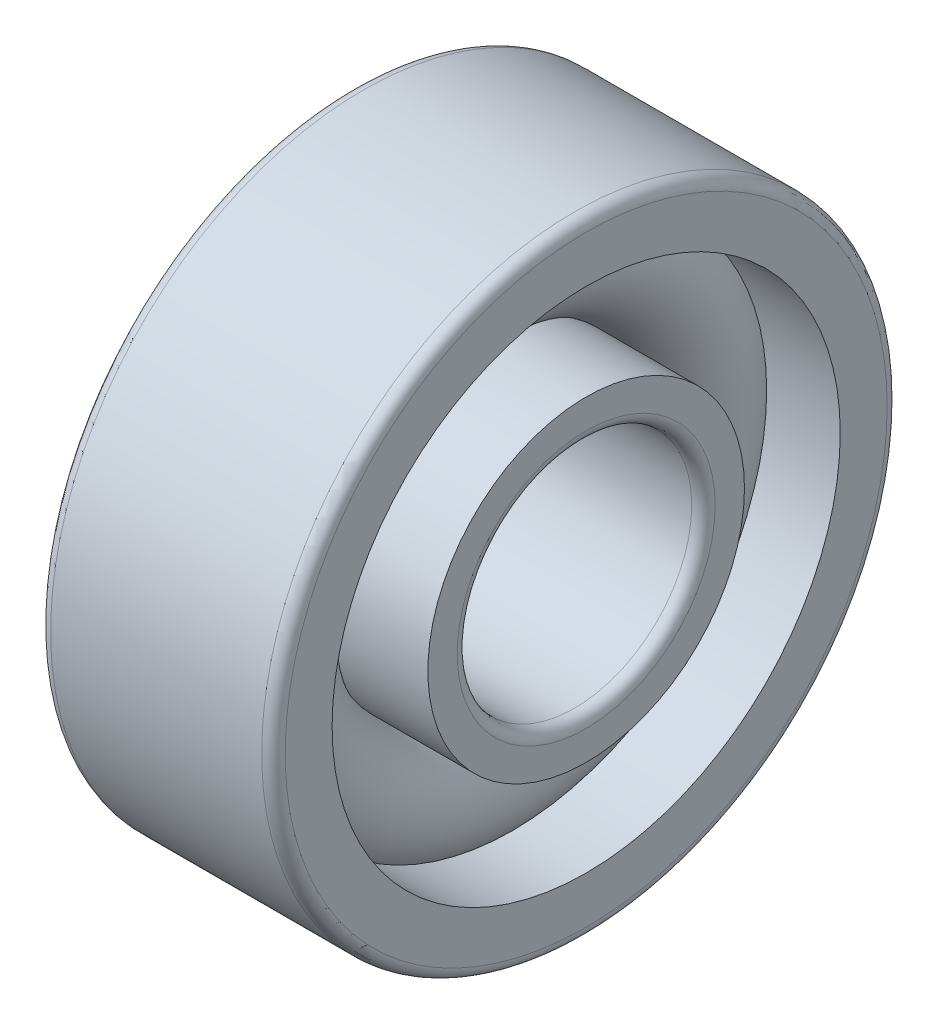
SolidWorks part; units mm, degrees
ref_plane "Plane1" through (0, 0, 0) normal (0, 0, 1) x (1, 0, 0)
ref_plane "Plane2" through (0, 0, 0) normal (0, 1, 0) x (1, 0, 0)
ref_plane "Plane3" through (0, 0, 0) normal (1, 0, 0) x (0, 0, -1)
sketch "Clipboard" plane through (0, 0, 0) normal (0, 0, 1) x (1, 0, 0)
  line L0 (-10, 0) -> (10, 0) construction
  line L1 (0, 0) -> (22.3471, -0.7804)
  line L2 (0, 0) -> (2.7483, 0.096)
  line L3 (0, 0) -> (22.3471, -0.7804)
  line L4 (0, 0) -> (-22.3573, -0.3902)
sketch "CagSpiSke" plane through (0, 0, 0) normal (0, 0, 1) x (1, 0, 0)
  line L0 (0.1875, 2.625) -> (0.1875, 2.875)
  line L1 (0.1875, 2.875) -> (-0.1875, 2.875)
  line L2 (-0.1875, 2.875) -> (-0.1875, 2.625)
  line L3 (-0.1875, 2.625) -> (0.1875, 2.625)
  line L4 (-20.6375, 0) -> (20.6375, 0) construction
  line L5 (0, 0) -> (0, 23.7692) construction
revolve "CageSpine" add sketch "CagSpiSke" angle 0.001 about L4
ref_axis "Axis1" through (-50, 0, 0) along (1, 0, 0)
sketch "CagBalSke" plane through (0, 0, 0) normal (0, 0, 1) x (1, 0, 0)
  line L0 (-0.825, 2.75) -> (0.825, 2.75)
  line L1 (-1.905, 2.75) -> (1.905, 2.75) construction
  line L2 (-10, 0) -> (10, 0) construction
  line L3 (0, 0) -> (0, 24) construction
  arc A0 (0.825, 2.75) -> (-0.825, 2.75) centre (0, 2.75) cw
revolve "CageBall" [suppressed] add sketch "CagBalSke" angle 360 about L1 reverse direction yes
pattern_circular "CageBalls" [suppressed] count 2 every 180 about axis through (-50, 0, 0) along (1, 0, 0)
sketch "CagTrmODSke" plane through (0, 0, 0) normal (0, 0, 1) x (1, 0, 0)
  line L0 (0.826, 2.875) -> (0.826, 3.576)
  line L1 (0.826, 3.576) -> (-0.826, 3.576)
  line L2 (-0.826, 3.576) -> (-0.826, 2.875)
  line L3 (-0.826, 2.875) -> (0.826, 2.875)
  line L4 (-20.6375, 0) -> (20.6375, 0) construction
  line L5 (0, 0) -> (0, 25) construction
revolve "CageTrimOD" [suppressed] cut sketch "CagTrmODSke" angle 360 about L4 reverse direction yes
sketch "CagTrmIDSke" plane through (0, 0, 0) normal (0, 0, 1) x (1, 0, 0)
  line L0 (0.826, 1.926) -> (0.826, 2.625)
  line L1 (0.826, 2.625) -> (-0.826, 2.625)
  line L2 (-0.826, 2.625) -> (-0.826, 1.926)
  line L3 (-0.826, 1.926) -> (0.826, 1.926)
  line L4 (-20.6375, 0) -> (20.6375, 0) construction
  line L5 (0, 0) -> (0, 25) construction
revolve "CageTrimID" [suppressed] cut sketch "CagTrmIDSke" angle 360 about L4 reverse direction yes
sketch "BalSimSke" plane through (0, 0, 0) normal (0, 0, 1) x (1, 0, 0)
  line L0 (-10, 0) -> (10, 0) construction
  line L1 (-10, 2.75) -> (10, 2.75) construction
  line L2 (0, 0) -> (0, 23) construction
  circle A0 centre (0, 2.75) radius 0.75
revolve "BallsSimplified" add sketch "BalSimSke" angle 360 about L0
sketch "BalDetSke" plane through (0, 0, 0) normal (0, 0, 1) x (1, 0, 0)
  line L0 (-0.75, 2.75) -> (0.75, 2.75)
  line L1 (-1.905, 2.75) -> (1.905, 2.75) construction
  line L2 (0, 0) -> (0, 25) construction
  arc A0 (0.75, 2.75) -> (-0.75, 2.75) centre (0, 2.75) cw
revolve "BallDetailed" [suppressed] add sketch "BalDetSke" angle 360 about L1 reverse direction yes
sketch "InnRacSke" plane through (0, 0, 0) normal (0, 0, 1) x (1, 0, 0)
  line L0 (-0.525, 2.25) -> (-1.5, 2.25)
  line L1 (-1.5, 2.25) -> (-1.5, 1.65)
  line L2 (-1.35, 1.5) -> (1.35, 1.5)
  line L3 (1.5, 1.65) -> (1.5, 2.025)
  line L4 (0, 2.025) -> (1.5, 2.025)
  line L5 (-20.6375, 0) -> (20.6375, 0) construction
  line L6 (0, 0) -> (0, 30) construction
  arc A0 (-1.5, 1.65) -> (-1.35, 1.5) centre (-1.35, 1.65) ccw
  arc A1 (1.35, 1.5) -> (1.5, 1.65) centre (1.35, 1.65) ccw
  arc A2 (0, 2.025) -> (-0.525, 2.25) centre (0, 2.75) cw
  dimension "Fillet_radius" = 0.15
revolve "InnerRace" add sketch "InnRacSke" angle 360 about L5 reverse direction yes
sketch "OutRacSke" plane through (0, 0, 0) normal (0, 0, 1) x (1, 0, 0)
  line L0 (0, 3.475) -> (-1.5, 3.475)
  line L1 (-1.5, 3.475) -> (-1.5, 3.85)
  line L2 (-1.35, 4) -> (1.35, 4)
  line L3 (1.5, 3.85) -> (1.5, 3.25)
  line L4 (1.5, 3.25) -> (0.525, 3.25)
  line L5 (-20.6375, 0) -> (20.6375, 0) construction
  line L6 (0, 0) -> (0, 30) construction
  arc A0 (-1.5, 3.85) -> (-1.35, 4) centre (-1.35, 3.85) cw
  arc A1 (1.35, 4) -> (1.5, 3.85) centre (1.35, 3.85) cw
  arc A2 (0.525, 3.25) -> (0, 3.475) centre (0, 2.75) ccw
  dimension "Fillet_radius" = 0.15
revolve "OuterRace" add sketch "OutRacSke" angle 360 about L5 reverse direction yes
pattern_circular "BallsDetailed" [suppressed] count 2 every 180 about axis through (-50, 0, 0) along (1, 0, 0)
equation "\"BallCLRad@Clipboard\" = ( \"OD@OutRacSke\" + \"ID@InnRacSke\" ) / 4"
equation "\"BallCLRad@BalSimSke\" = \"BallCLRad@Clipboard\""
equation "\"BallCLRad@BalDetSke\" = \"BallCLRad@Clipboard\""
equation "\"BallCLRad@InnRacSke\" = \"BallCLRad@Clipboard\""
equation "\"BallCLRad@OutRacSke\" = \"BallCLRad@Clipboard\""
equation "\"Ball_diameter@InnRacSke\" = \"Ball_diameter@BalDetSke\" - 0.05"
equation "\"Ball_diameter@OutRacSke\" = \"Ball_diameter@BalDetSke\" - 0.05"
equation "\"Ball_diameter@BalSimSke\" = \"Ball_diameter@BalDetSke\""
equation "\"Width@OutRacSke\" = \"Width@InnRacSke\""
equation "\"Fillet_radius@OutRacSke\" = \"Fillet_radius@InnRacSke\""
equation "\"Max_count@Clipboard\" = int( 3.14159265 / atn(( \"Ball_diameter@BalDetSke\" / 2) / sqr( \"BallCLRad@Clipboard\"  *  \"BallCLRad@Clipboard\" - ( \"Ball_diameter@BalDetSke\" / 2) *  ( \"Ball_diameter@BalDetSke\" / 2))))"
equation "\"Max_count@Clipboard\" = ((sgn( \"Max_count@Clipboard\" - \"Count@Clipboard\" )-1)*( \"Max_count@Clipboard\" - \"Count@Clipboard\" ))/-2+ \"Count@Clipboard\""
equation "\"Count@BallsDetailed\" = int( \"Show_count@Clipboard\" ) "
equation "\"Count@BallsDetailed\" = ((sgn( \"Count@BallsDetailed\" - \"Max_count@Clipboard\" )-1)*( \"Count@BallsDetailed\" - \"Max_count@Clipboard\" ))/-2+ \"Max_count@Clipboard\""
equation "\"Count@BallsDetailed\" = ((sgn( \"Count@BallsDetailed\" - \"Min_count@Clipboard\" )+1)*( \"Count@BallsDetailed\" - \"Min_count@Clipboard\"))/2 +\"Min_count@Clipboard\""
equation "\"Angle@BallsDetailed\" = 360.0 / \"Max_count@Clipboard\""
equation "\"BallCLRad@CagBalSke\" = \"BallCLRad@Clipboard\""
equation "\"Count@CageBalls\" = \"Count@BallsDetailed\""
equation "\"Angle@CageBalls\" = \"Angle@BallsDetailed\""
equation "\"Angle@CageSpine\" =  \"Angle@CageBalls\" * ( \"Count@CageBalls\" -1 + int( \"Count@CageBalls\" / \"Max_count@Clipboard\" ) )  + 0.001 -  int( \"Count@CageBalls\" / \"Max_count@Clipboard\" ) * 0.001"
equation "\"Angle@CageSpine\" =  \"Angle@CageSpine\" * int( \"Min_count@Clipboard\" / 2) + int(1 / \"Min_count@Clipboard\")  * 0.001"
equation "\"CageWallOD@CagBalSke\" =  \"Ball_diameter@BalDetSke\" * 1.1"
equation "\"Thickness@CagSpiSke\" =  \"Ball_diameter@BalDetSke\" * 0.25"
equation "\"OD@CagTrmODSke\" = \"BallCLRad@Clipboard\" * 2 + \"CageWallOD@CagBalSke\" + 0.002"
equation "\"ID@CagTrmODSke\" = \"BallCLRad@Clipboard\" * 2 + \"Ball_diameter@BalDetSke\" / 6"
equation "\"OD@CagTrmIDSke\" = \"BallCLRad@Clipboard\" * 2 - \"Ball_diameter@BalDetSke\" / 6"
equation "\"ID@CagTrmIDSke\" = \"BallCLRad@Clipboard\" * 2 - \"CageWallOD@CagBalSke\" + 0.002"
equation "\"OD@CagSpiSke\" = \"ID@CagTrmODSke\""
equation "\"ID@CagSpiSke\" = \"OD@CagTrmIDSke\""
equation "\"Width@CagTrmODSke\" = \"CageWallOD@CagBalSke\" + 0.002"
equation "\"Width@CagTrmIDSke\" = \"CageWallOD@CagBalSke\" + 0.002"
